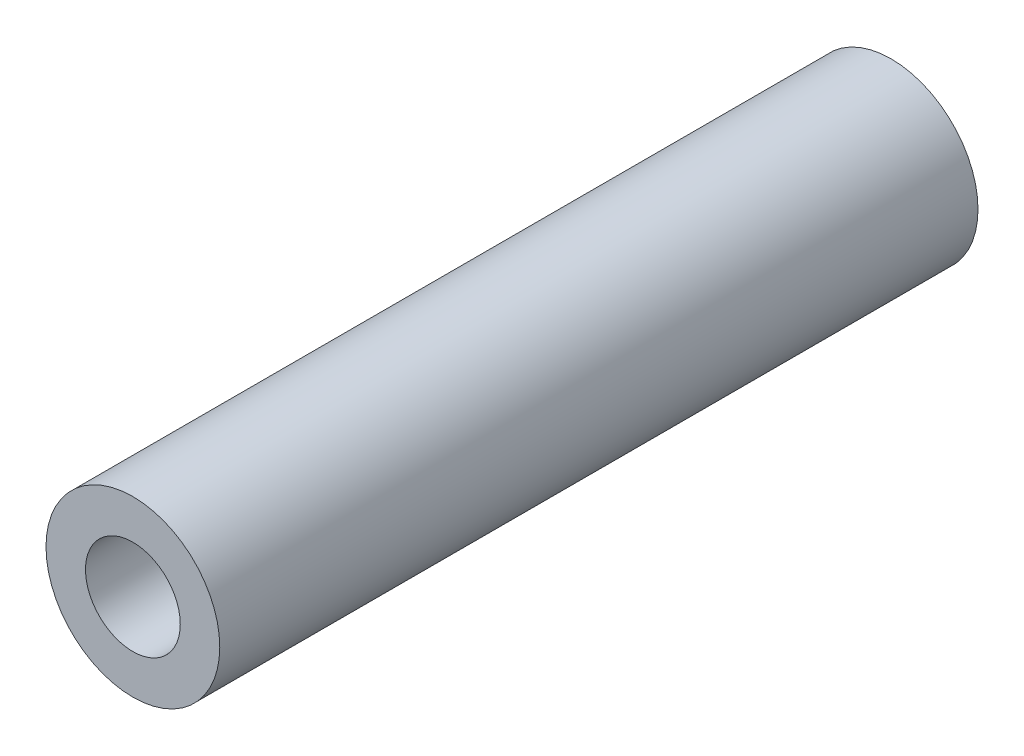
SolidWorks part; units mm, degrees
material "Silicon Rubber"
ref_plane "X-Y Datum" through (0, 0, 0) normal (0, 0, 1) x (1, 0, 0)
ref_plane "X-Z Datum" through (0, 0, 0) normal (0, 1, 0) x (1, 0, 0)
ref_plane "Y-Z Datum" through (0, 0, 0) normal (1, 0, 0) x (0, 0, -1)
sketch3d "3DSketch1"
  line L0 (0, 0, 0) -> (0, 0, 76.2)
  point P3 (0, 0, 0)
  dimension "D1" = 76.2
sweep "Sweep1" add path "3DSketch1" circular profile diameter 17.4625 parameters "D3"=17.4625
sweep "Cut-Sweep1" cut path "3DSketch1<2>" circular profile diameter 9.525 parameters "D3"=9.525
sketch3d "3DSketch1<2>" same geometry as "3DSketch1"
